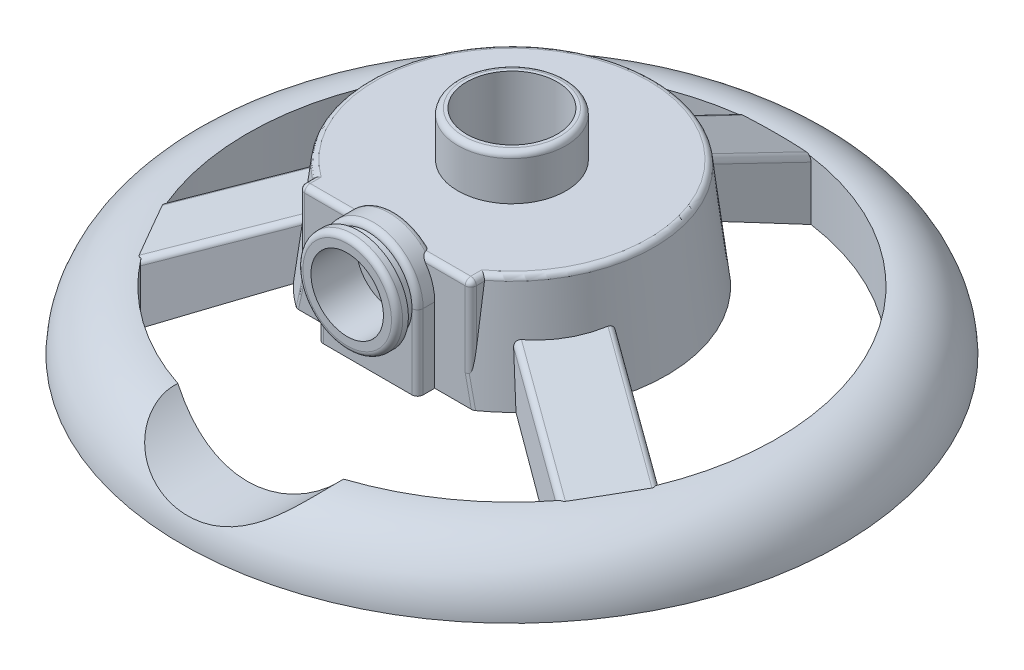
SolidWorks part; units mm, degrees
material "ABS"
ref_plane "Front Plane" through (0, 0, 0) normal (0, 0, 1) x (1, 0, 0)
ref_plane "Top Plane" through (0, 0, 0) normal (0, 1, 0) x (1, 0, 0)
ref_plane "Right Plane" through (0, 0, 0) normal (1, 0, 0) x (0, 0, -1)
other "Configuration Table"
sketch "Sketch1" plane through (0, 0, 0) normal (0, 1, 0) x (1, 0, 0)
  circle A0 centre (0, 0) radius 75.057
  dimension "D1" = 150.114
extrude "Boss-Extrude1" add sketch "Sketch1" along normal blind 48.5648
sketch "Sketch2" plane through (0, 0, 0) normal (0, 1, 0) x (1, 0, 0)
  circle A0 centre (0, 0) radius 12.319
  circle A1 centre (0, 0) radius 79.7227
  dimension "D1" = 24.638
extrude "Cut-Extrude1" cut sketch "Sketch2" against normal blind 10.1854 from surface starting at face at (0, 48.5648, 75.057)
sketch "Sketch3" plane through (0, 0, 0) normal (0, 0, 1) x (1, 0, 0)
  line L0 (32.2326, 38.3794) -> (36.83, 0)
  line L1 (75.057, 38.3794) -> (-75.057, 38.3794) construction
  line L2 (-75.057, 0) -> (75.057, 0) construction
  line L3 (36.83, 0) -> (60.2488, 0)
  line L4 (60.2488, 0) -> (60.2488, 38.3794)
  line L5 (60.2488, 38.3794) -> (32.2326, 38.3794)
  line L6 (12.319, 38.3794) -> (12.319, 48.5648) construction
  dimension "D1" = 19.9136
  dimension "D2" = 36.83
  dimension "D3" = 23.4188
revolve "Cut-Revolve1" cut sketch "Sketch3" angle 360 about axis through (0, 48.5648, 0) along (0, -1, 0)
sketch "Sketch5" plane through (0, 0, 0) normal (1, 0, 0) x (0, 0, -1)
  line L0 (30.2771, 27.8892) -> (65.5466, 10.8712)
  line L1 (65.5466, 10.8712) -> (65.5466, 0)
  line L2 (-75.057, 0) -> (75.057, 0) construction
  line L3 (65.5466, 0) -> (30.2771, 0)
  line L4 (-36.83, 0) -> (36.83, 0) construction
  line L5 (30.2771, 0) -> (30.2771, 27.8892)
  line L6 (32.2326, 38.3794) -> (-32.2326, 38.3794) construction
  dimension "D1" = 10.4902
  dimension "D2" = 10.8712
extrude "Boss-Extrude2" add sketch "Sketch5" along normal mid plane 16.9672
sketch "Sketch7" plane through (0, 0, 0) normal (1, 0, 0) x (0, 0, -1)
  line L0 (0, 0) -> (0, 64.7969) construction
sketch "Sketch8" plane through (0, 0, 0) normal (1, 0, 0) x (0, 0, -1)
  line L0 (60.2488, 38.3794) -> (81.2598, 24.4144)
  line L1 (75.057, 38.3794) -> (-75.057, 38.3794) construction
  line L2 (60.2488, 38.3794) -> (-60.2488, 38.3794) construction
  line L3 (81.2598, 24.4144) -> (81.2598, 44.4632)
  line L4 (81.2598, 44.4632) -> (60.2488, 38.3794)
revolve "Cut-Revolve11" cut sketch "Sketch8" angle 360 about L0
sketch "Sketch9" plane through (0, 0, 0) normal (1, 0, 0) x (0, 0, -1)
  line L0 (60.2488, 13.4274) -> (60.2488, 39.7781)
  line L1 (60.2488, 39.7781) -> (78.2238, 27.9631)
  line L2 (78.2238, 27.9631) -> (75.057, 0)
  arc A0 (75.057, 0) -> (60.2488, 13.4274) centre (60.9392, -0.6904) ccw
revolve "Cut-Revolve13" cut sketch "Sketch9" angle 360 about L0
pattern_circular "CirPattern1" count 3 over 360 about axis through (0, 0, 0) along (0, 1, 0) of "Boss-Extrude2" reverse direction yes
sketch "Sketch11" plane through (0, 0, 0) normal (1, 0, 0) x (0, 0, -1)
  line L0 (-60.2488, 0) -> (-35.2195, 13.4443)
  line L3 (-35.2195, 13.4443) -> (0, 13.4274)
  line L6 (0, 13.4274) -> (0, 0)
  line L7 (0, 0) -> (-60.2488, 0)
revolve "Cut-Revolve14" cut sketch "Sketch11" angle 360 about L0
sketch "Sketch12" plane through (0, 0, 0) normal (0, 1, 0) x (1, 0, 0)
  line L1 (-19.558, -25.4) -> (19.558, -25.4)
  line L2 (-19.558, -25.4) -> (-19.558, -28.9306)
  line L3 (-19.558, -28.9306) -> (19.558, -28.9306)
  line L4 (19.558, -25.4) -> (19.558, -28.9306)
  circle A1 centre (0, 0) radius 32.2326 construction
  point P7 (0, -25.4)
  dimension "D1" = 25.4
  dimension "D2" = 3.5306
  dimension "D3" = 39.116
extrude "Boss-Extrude3" add sketch "Sketch12" against normal up to surface (24.9366 mm away) from surface up to face at (0, 13.4443, 0) starting at face at (0, 38.3794, 12.319)
sketch "Sketch13" plane through (0, 0, 0) normal (0, 1, 0) x (1, 0, 0)
  line L1 (-21.5562, -28.9306) -> (20.7538, -28.9306)
  line L2 (-21.5562, -28.9306) -> (-21.5562, -36.4977)
  line L3 (-21.5562, -36.4977) -> (20.7538, -36.4977)
  line L4 (20.7538, -28.9306) -> (20.7538, -36.4977)
extrude "Cut-Extrude2" cut sketch "Sketch13" along normal through all both and the other way through all
sketch "Sketch14" plane through (0, 0, 0) normal (0, 0, 1) x (1, 0, 0)
  line L0 (0, 0) -> (0, 64.7969) construction
  line L1 (19.558, 38.3794) -> (-19.558, 38.3794) construction
  circle A0 centre (0, 30.5054) radius 11.3538
  dimension "D1" = 22.7076
  dimension "D2" = 7.874
extrude "Boss-Extrude4" add sketch "Sketch14" along normal blind 10.8458 from offset 26.67
sketch "Sketch15" plane through (0, 0, 0) normal (0, 0, 1) x (1, 0, 0)
  line L0 (0, 0) -> (0, 64.7969) construction
  circle A0 centre (0, 30.5054) radius 10.0838
  circle A1 centre (0, 30.5054) radius 11.3538 construction
  circle A2 centre (0, 30.5054) radius 13.4177
  dimension "D1" = 20.1676
extrude "Cut-Extrude3" cut sketch "Sketch15" against normal blind 2.0828 from offset 34.925
sketch "Sketch16" plane through (0, 0, 0) normal (0, 1, 0) x (1, 0, 0)
  line L1 (11.3538, -32.8422) -> (-11.3538, -32.8422)
  line L2 (11.3538, -32.8422) -> (11.3538, -26.6758)
  line L3 (11.3538, -26.6758) -> (-11.3538, -26.6758)
  line L4 (-11.3538, -32.8422) -> (-11.3538, -26.6758)
extrude "Boss-Extrude6" add sketch "Sketch16" along normal blind 30.48
sketch "Sketch17" plane through (0, 0, 0) normal (0, 0, 1) x (1, 0, 0)
  line L0 (11.3538, 30.48) -> (11.3538, 0) construction
  line L1 (-11.3538, 13.4423) -> (11.3538, 13.4423)
  line L2 (-11.3538, 13.4423) -> (-11.3538, 0)
  line L3 (-11.3538, 0) -> (11.3538, 0)
  line L4 (11.3538, 13.4423) -> (11.3538, 0)
extrude "Cut-Extrude4" cut sketch "Sketch17" along normal blind 35.56
sketch "Sketch18" plane through (0, 0, 0) normal (0, 0, 1) x (1, 0, 0)
  line L0 (0, 0) -> (0, 64.7969) construction
  circle A0 centre (0, 30.5054) radius 8.255
  circle A1 centre (0, 30.5054) radius 11.3538 construction
  dimension "D1" = 16.51
hole_wizard "#97 (0.65) Diameter Hole1" positions "Sketch19" profile "Sketch20" hole size "#97" standard "ANSI Inch"
sketch "Sketch19" plane through (0, 0, 37.5158) normal (0, 0, 1) x (1, 0, 0)
  point P0 (0, 30.5054)
sketch "Sketch20" plane through (0, 30.5054, 37.5158) normal (1, 0, 0) x (0, -1, 0)
  line L0 (0, 0) -> (0, 10.3632)
  line L1 (0, 10.3632) -> (8.255, 10.3632)
  line L2 (8.255, 10.3632) -> (8.255, 0)
  line L5 (8.255, 0) -> (0, 0)
  line L10 (0, 10.3632) -> (-8.255, 10.3632) construction
  line L11 (0, -6.35) -> (0, 107.95) construction
  dimension "Hole Dia." = 16.51
  dimension "Hole Depth" = 10.3632
  dimension "Drill Angle" = 180
sketch "Sketch21" plane through (0, 0, 0) normal (0, 0, 1) x (1, 0, 0)
  circle A0 centre (0, 30.5054) radius 5.969
  dimension "D1" = 11.938
extrude "Cut-Extrude6" cut sketch "Sketch21" along normal blind 40.64
hole_wizard "7/8-14 Tapped Hole1" positions "Sketch22" profile "Sketch23" tap size "7/8-14" standard "ANSI Inch"
sketch "Sketch22" plane through (0, 48.5648, 0) normal (0, 1, 0) x (1, 0, 0)
  point P0 (0, 0)
sketch "Sketch23" plane through (0, 48.5648, 0) normal (1, 0, 0) x (0, 0, 1)
  line L0 (0, 0) -> (0, 25.4)
  line L1 (0, 25.4) -> (10.3187, 25.4)
  line L2 (10.3187, 25.4) -> (10.3188, 0)
  line L5 (10.3188, 0) -> (0, 0)
  line L10 (0, 25.4) -> (-10.3188, 25.4) construction
  line L11 (0, -6.35) -> (0, 107.95) construction
  dimension "Tap Drill Dia." = 20.6375
  dimension "Tap Drill Depth" = 25.4
  dimension "Drill Angle" = 180
cosmetic thread "Hole Thread1" parameters "D1"=44.45, "D2"=22.225
sketch "Sketch24" plane through (0, 0, 0) normal (0, 0, 1) x (1, 0, 0)
  circle A0 centre (0, 30.5054) radius 25.4506
extrude "Cut-Extrude7" cut sketch "Sketch24" along normal blind 40.64 from offset 40.64
fillet "Fillet1" radius 1.27 5 edges at (-19.558, 38.3794, 27.2757) (19.558, 38.3794, 27.2757) (-13.8689, 38.3794, 28.9306) (13.8689, 38.3794, 28.9306) (0, 38.3794, -32.2326)
fillet "Fillet2" radius 1.27 5 edges at (-19.186, 38.0074, 28.5586) (19.186, 38.0074, 28.5586) (-19.558, 26.5218, 28.9306) (19.558, 26.5218, 28.9306) (0, 48.5648, 12.319)
fillet "Fillet4" radius 1.27 6 edges at (-8.4836, 20.2592, -46.09) (8.4836, 20.2592, -46.09) (-44.4022, 20.1226, 15.8396) (-35.9186, 20.1226, 30.5337) (35.9186, 20.1226, 30.5337) (44.4022, 20.1226, 15.8396)
fillet "Fillet5" radius 1.27 3 edges at (0, 41.8592, 26.67) (0, 41.8592, 32.8422) (11.3538, 30.5054, 37.5158)
fillet "Fillet6" radius 1.27 2 edges
fillet "Fillet7" radius 1.27 2 edges at (-11.3538, 21.9612, 32.8422) (11.3538, 21.9612, 32.8422)
